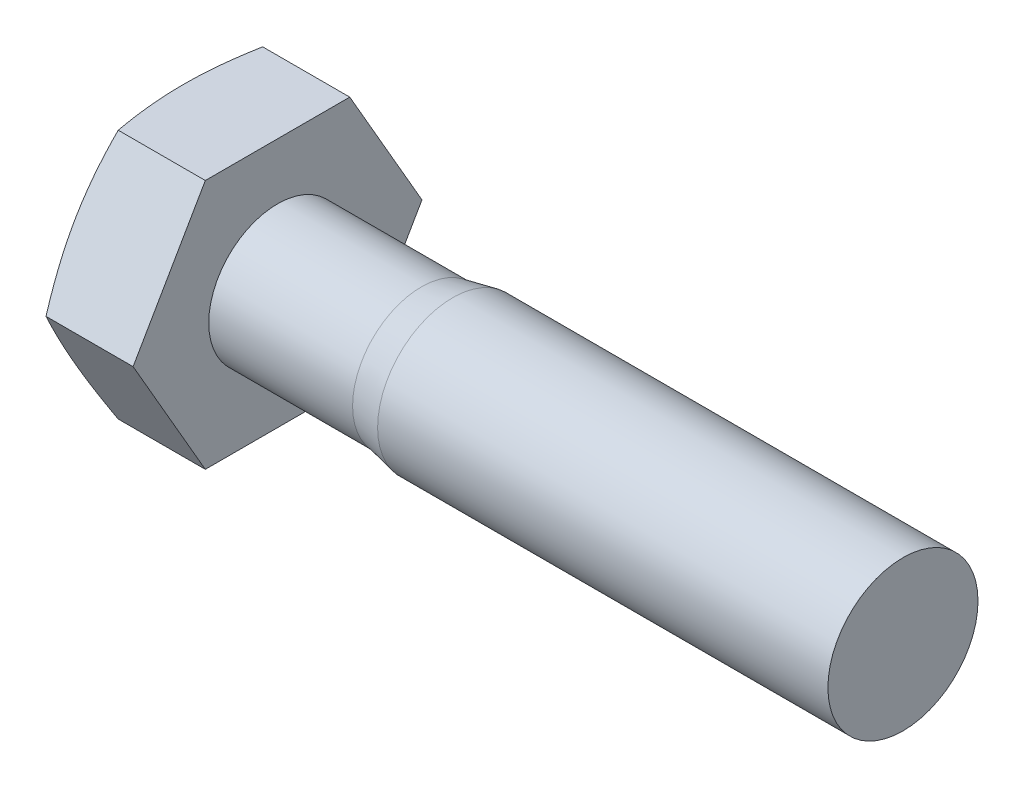
SolidWorks part; units mm, degrees
ref_plane "Front" through (0, 0, 0) normal (0, 0, 1) x (1, 0, 0)
ref_plane "Top" through (0, 0, 0) normal (0, 1, 0) x (1, 0, 0)
ref_plane "Right" through (0, 0, 0) normal (1, 0, 0) x (0, 0, -1)
sketch "Sketch1" plane through (0, 0, 0) normal (1, 0, 0) x (0, 0, -1)
  line L1 (5.7735, 0) -> (2.8868, 5)
  line L2 (2.8868, 5) -> (-2.8868, 5)
  line L3 (-2.8868, 5) -> (-5.7735, 0)
  line L4 (-5.7735, 0) -> (-2.8868, -5)
  line L5 (-2.8868, -5) -> (2.8868, -5)
  line L6 (2.8868, -5) -> (5.7735, 0)
  circle A0 centre (0, 0) radius 5 construction
  dimension "s" = 10
extrude "BaseHead" add sketch "Sketch1" along normal blind 4
ref_plane "Plane1" through (11, 0, 0) normal (1, 0, 0) x (0, 0, -1)
sketch "Sketch2" plane through (4, 0, 0) normal (1, 0, 0) x (0, 0, -1)
  circle A0 centre (0, 0) radius 3
extrude "BaseBody" add sketch "Sketch2" along normal blind 25
cosmetic thread "ThreadCosmetic1" [suppressed] parameters "b"=18, "D2"=4.917
sketch "Sketch3" plane through (3.1612, 0, 2.6123) normal (0, 1, 0) x (0, 0, -1)
  line L0 (2.6123, 5.2326) -> (2.6123, 1.6388) construction
  line L2 (8.3858, 3.1612) -> (8.3858, 2.6431)
  line L3 (8.3858, 2.6431) -> (6.9623, 3.1612)
  line L5 (6.9623, 3.1612) -> (8.3858, 3.1612)
  dimension "D1" = 20
  dimension "dw" = 8.7
revolve "HeadChamfer" cut sketch "Sketch3" angle 360 about L0
sketch "Sketch4" plane through (0, 0, 0) normal (-1, 0, 0) x (0, 0, 1)
  circle A0 centre (0, 0) radius 3.4
  dimension "da" = 6.8
extrude "Cut-Extrude1" cut sketch "Sketch4" against normal blind 0.8
sketch "Sketch5" plane through (-2.6796, 0, 8.1796) normal (0, 1, 0) x (0, 0, -1)
  line L0 (8.1796, 0.0175) -> (8.1796, -16.2361) construction
  line L2 (11.1796, -13.6796) -> (10.9296, -12.4296)
  line L4 (10.9296, -12.4296) -> (10.9296, -6.6796)
  line L6 (10.9296, -6.6796) -> (13.6796, -6.6796)
  line L7 (13.6796, -6.6796) -> (13.6796, -13.6796)
  line L8 (13.6796, -13.6796) -> (11.1796, -13.6796)
  line L11 (8.1796, -31.6796) -> (8.1796, -6.6796) construction
  line L14 (11.0664, -6.6796) -> (5.2929, -6.6796) construction
  line L16 (5.1796, -31.6796) -> (11.1796, -31.6796) construction
  line L17 (11.1796, -31.6796) -> (11.1796, -6.6796) construction
  dimension "D4" = 11
  dimension "D3" = 18
revolve "Cut-Revolve1" cut sketch "Sketch5" angle 360 about L0
fillet "HeadFillet" [suppressed] radius 0.25
sketch "Sketch6" plane through (0, 0, 0) normal (0, 1, 0) x (1, 0, 0)
  line L0 (28.7293, 3.5415) -> (29.2708, 3.5415)
  line L1 (29.2708, 3.5415) -> (29.2708, 3)
  line L2 (29.2708, 3) -> (29, 2.531)
  line L3 (29, 2.531) -> (28.7293, 3)
  line L4 (28.7293, 3) -> (28.7293, 3.5415)
  line L5 (29, -3) -> (29, 3) construction
  line L6 (29, 3) -> (11, 3) construction
  dimension "D1" = 0.5415
revolve "Cut-Revolve10" [suppressed] cut sketch "Sketch6" angle 360
pattern_linear "LPattern10" [suppressed] count 28 of bodies 106
equation "\"D1@Cut-Extrude1\" = 0.2 * \"k@BaseHead\""
equation "\"b@ThreadCosmetic1\" = \"l@BaseBody\" - \"lg@Plane1\""
equation "\"D4@Sketch5\" = 2 * \"ds@Sketch5\""
equation "\"D3@Sketch5\" = \"l@BaseBody\" - \"lg@Plane1\""
equation "\"D1@Sketch6\" =  ( \"d@Sketch2\" - \"D2@ThreadCosmetic1\" )  / 2"
equation "\"pitch@LPattern10\" = 1.2 * \"D1@Sketch6\""
equation "\"D1@LPattern10\" = \"b@ThreadCosmetic1\" / \"pitch@LPattern10\""
